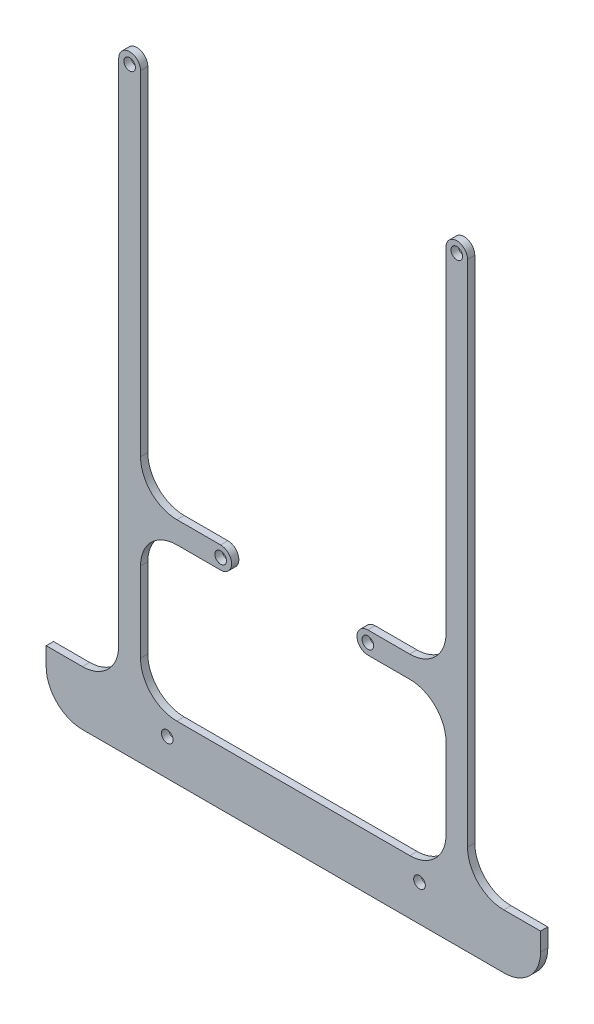
SolidWorks part; units mm, degrees
ref_plane "Front Plane" through (0, 0, 0) normal (0, 0, 1) x (1, 0, 0)
ref_plane "Top Plane" through (0, 0, 0) normal (0, 1, 0) x (1, 0, 0)
ref_plane "Right Plane" through (0, 0, 0) normal (1, 0, 0) x (0, 0, -1)
sketch "Sketch1" plane through (0, 0, 0) normal (0, 0, 1) x (1, 0, 0)
  line L0 (-48.0442, 75) -> (-48.0442, -65)
  line L5 (0, -75) -> (0, 75) construction
  line L6 (45, 0) -> (-45, 0) construction
  line L7 (-42.0442, 75) -> (-42.0442, -17)
  line L8 (42, 75) -> (42, -17)
  line L9 (47.9116, 75) -> (47.9116, -65.0442)
  line L10 (-58.0442, -75) -> (-68, -75)
  line L11 (57.8674, -75) -> (68, -75)
  line L12 (-68, -75) -> (-68, -80)
  line L13 (-58, -90) -> (58, -90)
  line L14 (68, -80) -> (68, -75)
  line L15 (-32.0442, -75) -> (32.0442, -75)
  line L16 (0, -75) -> (0, -80) construction
  line L17 (-34.7, -80) -> (34.7, -80)
  line L22 (-45, 0) -> (-20, 0) construction
  line L23 (-20, 0) -> (-20, -30) construction
  line L24 (-20, -30) -> (20.5, -30) construction
  line L25 (-20, -27) -> (-32.0442, -27)
  line L26 (-20, -33) -> (-32.0442, -33)
  line L27 (-42.0442, -43) -> (-42.0442, -65)
  line L28 (20.5, -27) -> (32, -27)
  line L29 (20.5, -33) -> (32.0442, -33)
  line L30 (42, -42.9558) -> (42, -65.0442)
  circle A0 centre (-45.0442, 75) radius 1.6
  circle A1 centre (44.9558, 75) radius 1.6
  arc A2 (-42.0442, 75) -> (-48.0442, 75) centre (-45.0442, 75) ccw
  arc A3 (47.9116, 75) -> (42, 75) centre (44.9558, 75) ccw
  arc A4 (-58, -90) -> (-68, -80) centre (-58, -80) cw
  arc A5 (58, -90) -> (68, -80) centre (58, -80) ccw
  circle A6 centre (-34.7, -80) radius 1.6
  circle A7 centre (34.7, -80) radius 1.6
  circle A8 centre (-20, -30) radius 1.6
  arc A9 (-20, -33) -> (-20, -27) centre (-20, -30) ccw
  circle A10 centre (20.5, -30) radius 1.6
  arc A11 (20.5, -27) -> (20.5, -33) centre (20.5, -30) ccw
  arc A12 (-32.0442, -75) -> (-42.0442, -65) centre (-32.0442, -65) cw
  arc A13 (-58.0442, -75) -> (-48.0442, -65) centre (-58.0442, -65) ccw
  arc A14 (-32.0442, -33) -> (-42.0442, -43) centre (-32.0442, -43) ccw
  arc A15 (-32.0442, -27) -> (-42.0442, -17) centre (-32.0442, -17) cw
  arc A16 (32, -27) -> (42, -17) centre (32, -17) ccw
  arc A17 (42, -42.9558) -> (32.0442, -33) centre (32.0442, -42.9558) ccw
  arc A18 (57.8674, -75) -> (47.9116, -65.0442) centre (57.8674, -65.0442) cw
  arc A19 (32.0442, -75) -> (42, -65.0442) centre (32.0442, -65.0442) ccw
  point P0 (0, 0)
  point P20 (-68, -90)
  point P26 (0, -75)
  point P28 (0, -80)
  point P50 (-42.0442, -33)
  point P57 (42, -33)
  dimension "D3" = 10
  dimension "D1" = 15
  dimension "D4" = 10
  dimension "D6" = 10
  dimension "D5" = 10
  dimension "D7" = 10
  dimension "D8" = 10
  dimension "D9" = 10
  dimension "D10" = 9.9558
  dimension "D11" = 9.9558
  dimension "D12" = 9.9558
  dimension "D2" = 90
  dimension "D13" = 69.4
  dimension "D14" = 40.5
extrude "Boss-Extrude1" add sketch "Sketch1" along normal blind 2 contours A19 L15 A12 L27 A14 L26 A9 L25 A15 L7 A2 L0 A13 L10 L12 A4 L13 A5 L14 L11 A18 L9 A3 L8 A16 L28 A11 L29 A17 L30 A10 A8 A7 A6 A1 A0 region at (-45.0442, 77.7839, 0)
